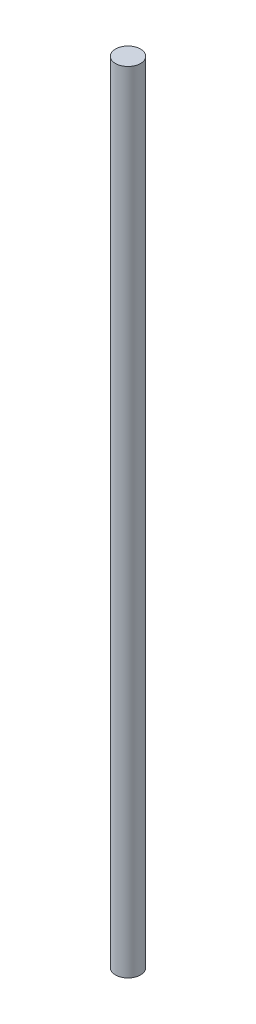
SolidWorks part; units mm, degrees
ref_plane "Front Plane" through (0, 0, 0) normal (0, 0, 1) x (1, 0, 0)
ref_plane "Top Plane" through (0, 0, 0) normal (0, 1, 0) x (1, 0, 0)
ref_plane "Right Plane" through (0, 0, 0) normal (1, 0, 0) x (0, 0, -1)
ref_axis "X" through (-88.99, 0, 0) along (1, 0, 0)
ref_axis "Y" through (0, 55, 0) along (0, -1, 0)
ref_axis "Z" through (0, 0, -88.99) along (0, 0, 1)
sketch "Sketch1" plane through (0, 0, 0) normal (0, 1, 0) x (1, 0, 0)
  circle A0 centre (0, 0) radius 0.7937
  dimension "D1" = 1.5875
extrude "Boss-Extrude1" add sketch "Sketch1" along normal blind 50
